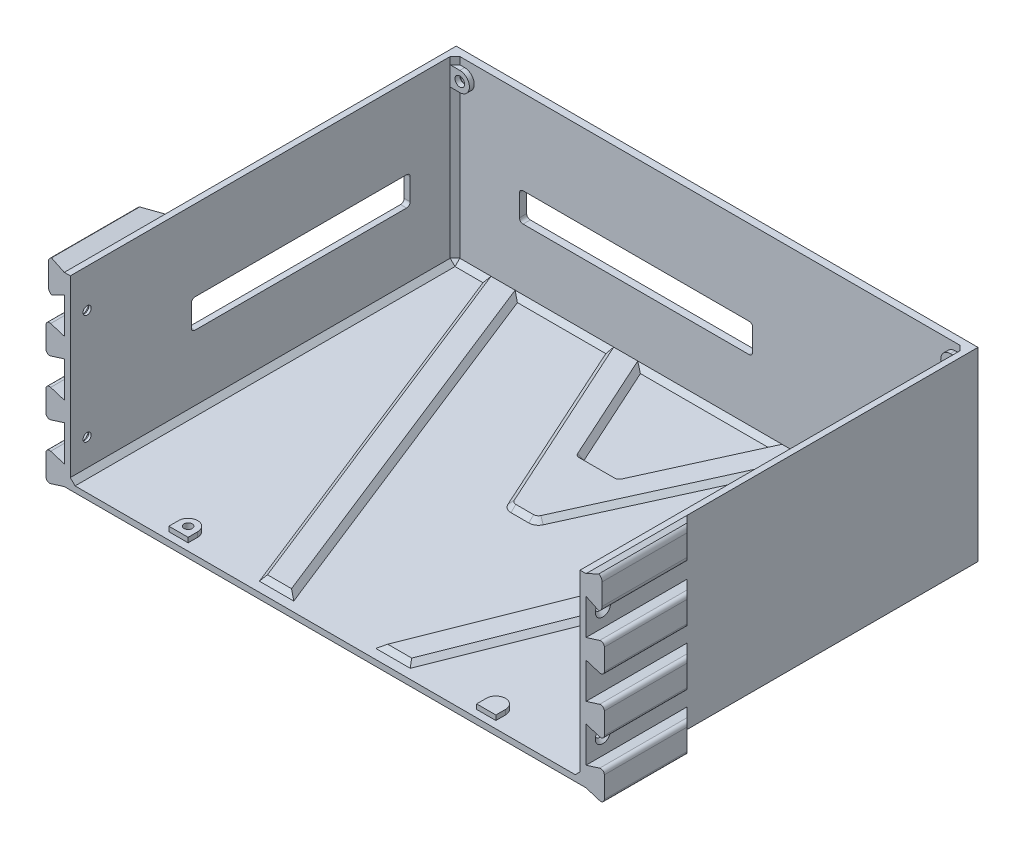
SolidWorks part; units mm, degrees
ref_plane "Płaszczyzna przednia" through (0, 0, 0) normal (0, 0, 1) x (1, 0, 0)
ref_plane "Płaszczyzna górna" through (0, 0, 0) normal (0, 1, 0) x (1, 0, 0)
ref_plane "Płaszczyzna prawa" through (0, 0, 0) normal (1, 0, 0) x (0, 0, -1)
sketch "Szkic1" plane through (0, 0, 0) normal (0, 0, 1) x (1, 0, 0)
  line L1 (0, 0) -> (217, 0)
  line L2 (0, 0) -> (0, 77.16)
  line L3 (0, 77.16) -> (217, 77.16)
  line L4 (217, 0) -> (217, 77.16)
  dimension "D1" = 77.16
  dimension "D2" = 217
extrude "Dodanie-wyciągnięcie1" add sketch "Szkic1" along normal blind 3
sketch "Szkic2" plane through (0, 0, 3) normal (0, 0, 1) x (1, 0, 0)
  line L0 (0, 77.16) -> (0, 0)
  line L1 (0, 0) -> (217, 0)
  line L2 (217, 0) -> (217, 77.16)
  line L3 (217, 77.16) -> (214.5, 77.16)
  line L4 (217, 77.16) -> (0, 77.16) construction
  line L5 (214.5, 77.16) -> (214.5, 2.5)
  line L6 (214.5, 2.5) -> (2.5, 2.5)
  line L7 (2.5, 2.5) -> (2.5, 77.16)
  line L8 (2.5, 77.16) -> (0, 77.16)
  dimension "D1" = 2.5
  dimension "D2" = 2.5
  dimension "D3" = 2.5
extrude "Dodanie-wyciągnięcie2" add sketch "Szkic2" along normal blind 160
sketch "Szkic3" plane through (0, 2.5, 0) normal (0, 1, 0) x (1, 0, 0)
  line L0 (17.5, -3) -> (78.5, -157)
  line L1 (214.5, -3) -> (2.5, -3) construction
  line L3 (27.5, -3) -> (88.5, -157)
  line L4 (214.5, -3) -> (2.5, -3) construction
  line L5 (101.1515, -50) -> (115.8485, -50)
  line L6 (78.5, -157) -> (88.5, -157)
  line L7 (17.5, -3) -> (27.5, -3)
  line L8 (199.5, -3) -> (138.5, -157)
  line L9 (138.5, -157) -> (128.5, -157)
  line L10 (128.5, -157) -> (138.5, -157)
  line L11 (128.5, -157) -> (189.5, -3)
  line L12 (189.5, -3) -> (199.5, -3)
  line L13 (217, 0) -> (0, 0) construction
  line L14 (68.5, -3) -> (102.9671, -78.8276)
  line L15 (114.0329, -78.8276) -> (148.5, -3)
  line L16 (138.5, -3) -> (117.6693, -48.8276)
  line L17 (99.3307, -48.8276) -> (78.5, -3)
  line L18 (104.7878, -80) -> (112.2122, -80)
  line L19 (68.5, -3) -> (78.5, -3)
  line L20 (138.5, -3) -> (148.5, -3)
  line L21 (108.5, 0) -> (108.5, -100) construction
  line L23 (214.5, -163) -> (2.5, -163) construction
  arc A0 (115.8485, -50) -> (117.6693, -48.8276) centre (115.8485, -48) ccw
  arc A1 (101.1515, -50) -> (99.3307, -48.8276) centre (101.1515, -48) cw
  arc A2 (112.2122, -80) -> (114.0329, -78.8276) centre (112.2122, -78) ccw
  arc A3 (104.7878, -80) -> (102.9671, -78.8276) centre (104.7878, -78) cw
  point P14 (108.5, 0)
  point P33 (113.5, -80)
  point P36 (103.5, -80)
  point P39 (108.5, -50)
  line M5 (214.5, -3) -> (2.5, -3)
  line M7 (2.5, -163) -> (214.5, -163)
  dimension "D16" = 2
  dimension "D1" = 20
  dimension "D2" = 15
  dimension "D3" = 40
  dimension "D4" = 10
  dimension "D5" = 15
  dimension "D6" = 10
  dimension "D7" = 10
  dimension "D8" = 10
  dimension "D9" = 10
  dimension "D10" = 10
  dimension "D11" = 10
  dimension "D12" = 5
  dimension "D13" = 60
  dimension "D14" = 80
  dimension "D15" = 30
  dimension "D17" = 6
extrude "Dodanie-wyciągnięcie3" add sketch "Szkic3" along normal blind 2 contours L3 L0 M5 M7 | L11 L8 M7 M5 | L20 L15 A2 L18 A3 L14 L19 L17 A1 L5 A0 L16 region at (53, 2.5, 80) region at (164, 2.5, 80)
chamfer "Sfazowanie2" distance 2 angle 45 25 edges at (169, 2.5, 80) (214.5, 39.83, 3) (214.5, 2.5, 83) (207, 2.5, 3) (58, 2.5, 80) (159, 2.5, 80) (169, 2.5, 3) (48, 2.5, 3) (48, 2.5, 80) (10, 2.5, 3) (2.5, 2.5, 83) (2.5, 39.83, 3) (108.5, 2.5, 3) (85.7335, 2.5, 40.9138) (103.7051, 2.5, 79.6815) (108.5, 2.5, 80) (113.2949, 2.5, 79.6815) (131.2665, 2.5, 40.9138) (128.0846, 2.5, 25.9138) (116.9313, 2.5, 49.6815) (108.5, 2.5, 50) (100.0687, 2.5, 49.6815) (88.9154, 2.5, 25.9138) (133.5, 2.5, 157) (83.5, 2.5, 157)
sketch "Szkic10" plane through (0, 0, 163) normal (0, 0, 1) x (1, 0, 0)
  line L0 (224.6, 87) -> (224.6, 0) construction
  line L1 (217, 0) -> (217, 77.16) construction
  line L2 (217, 0) -> (217, 8.16)
  line L3 (217, 0) -> (222.6526, -1.7665)
  line L4 (217, 8.16) -> (222.6526, 9.9265)
  line L5 (224.6, 8.4948) -> (224.6, -0.3348)
  line L6 (108.5, 77.16) -> (108.5, 114.4452) construction
  line L7 (212.5, 77.16) -> (4.5, 77.16) construction
  line L8 (217, 23) -> (217, 31.16)
  line L9 (217, 23) -> (222.6526, 21.2335)
  line L10 (217, 31.16) -> (222.6526, 32.9265)
  line L11 (224.6, 31.4948) -> (224.6, 22.6652)
  line L12 (217, 46) -> (217, 54.16)
  line L13 (217, 46) -> (222.6526, 44.2335)
  line L14 (217, 54.16) -> (222.6526, 55.9265)
  line L15 (224.6, 54.4948) -> (224.6, 45.6652)
  line L16 (-7.6, 54.4948) -> (-7.6, 45.6652)
  line L17 (0, 54.16) -> (-5.6526, 55.9265)
  line L18 (0, 46) -> (-5.6526, 44.2335)
  line L19 (0, 46) -> (0, 54.16)
  line L20 (-7.6, 31.4948) -> (-7.6, 22.6652)
  line L21 (0, 31.16) -> (-5.6526, 32.9265)
  line L22 (0, 23) -> (-5.6526, 21.2335)
  line L23 (0, 23) -> (0, 31.16)
  line L24 (-7.6, 8.4948) -> (-7.6, -0.3348)
  line L25 (0, 8.16) -> (-5.6526, 9.9265)
  line L26 (0, 0) -> (-5.6526, -1.7665)
  line L27 (0, 0) -> (0, 8.16)
  line L28 (217, 69) -> (217, 77.16)
  line L29 (217, 69) -> (222.3314, 66.4215)
  line L30 (217, 77.16) -> (222.3314, 79.7385)
  line L31 (223.6594, 77.4948) -> (223.6594, 68.6652)
  line L32 (-6.6594, 77.4948) -> (-6.6594, 68.6652)
  line L33 (0, 77.16) -> (-5.3314, 79.7385)
  line L34 (0, 69) -> (-5.3314, 66.4215)
  line L35 (0, 69) -> (0, 77.16)
  arc A0 (222.6526, -1.7665) -> (224.6, -0.3348) centre (223.1, -0.3348) ccw
  arc A1 (222.6526, 9.9265) -> (224.6, 8.4948) centre (223.1, 8.4948) cw
  arc A2 (222.6526, 21.2335) -> (224.6, 22.6652) centre (223.1, 22.6652) ccw
  arc A3 (222.6526, 32.9265) -> (224.6, 31.4948) centre (223.1, 31.4948) cw
  arc A4 (222.6526, 44.2335) -> (224.6, 45.6652) centre (223.1, 45.6652) ccw
  arc A5 (222.6526, 55.9265) -> (224.6, 54.4948) centre (223.1, 54.4948) cw
  arc A6 (-5.6526, 55.9265) -> (-7.6, 54.4948) centre (-6.1, 54.4948) ccw
  arc A7 (-5.6526, 44.2335) -> (-7.6, 45.6652) centre (-6.1, 45.6652) cw
  arc A8 (-5.6526, 32.9265) -> (-7.6, 31.4948) centre (-6.1, 31.4948) ccw
  arc A9 (-5.6526, 21.2335) -> (-7.6, 22.6652) centre (-6.1, 22.6652) cw
  arc A10 (-5.6526, 9.9265) -> (-7.6, 8.4948) centre (-6.1, 8.4948) ccw
  arc A11 (-5.6526, -1.7665) -> (-7.6, -0.3348) centre (-6.1, -0.3348) cw
  arc A12 (222.3314, 66.4215) -> (223.6594, 68.6652) centre (221.1, 68.6652) ccw
  arc A13 (222.3314, 79.7385) -> (223.6594, 77.4948) centre (221.1, 77.4948) cw
  arc A14 (-5.3314, 79.7385) -> (-6.6594, 77.4948) centre (-4.1, 77.4948) ccw
  arc A15 (-5.3314, 66.4215) -> (-6.6594, 68.6652) centre (-4.1, 68.6652) cw
  point P11 (224.6, -2.3751)
  point P14 (224.6, 10.5351)
  point P60 (-7.6, 10.5351)
  point P61 (-7.6, -2.3751)
  dimension "D5" = 1.5
  dimension "D1" = 7.6
  dimension "D2" = 8.16
  dimension "D3" = 23
  dimension "D4" = 34.71
  dimension "D6" = 3
extrude "Dodanie-wyciągnięcie6" add sketch "Szkic10" against normal blind 32
chamfer "Sfazowanie5" distance 10 angle 45 8 edges at (217, 50.08, 131) (217, 4.08, 131) (0, 4.08, 131) (0, 27.08, 131) (0, 50.08, 131) (217, 27.08, 131) (217, 73.08, 131) (0, 73.08, 131)
ref_plane "Płaszczyzna1" through (108.5, 0, 0) normal (-1, 0, 0) x (0, 0, 1)
sketch "Sketch1" plane through (0, 0, 0) normal (-1, 0, 0) x (0, 0, 1)
  line L4 (21.6472, 42.16) -> (21.6472, 33.16)
  line L5 (23.1472, 31.66) -> (111.1472, 31.66)
  line L6 (112.6472, 33.16) -> (112.6472, 42.16)
  line L7 (111.1472, 43.66) -> (23.1472, 43.66)
  line L8 (21.6472, 42.16) -> (21.6472, 33.16)
  line L9 (23.1472, 31.66) -> (111.1472, 31.66)
  line L10 (112.6472, 33.16) -> (112.6472, 42.16)
  line L11 (111.1472, 43.66) -> (23.1472, 43.66)
  arc A4 (23.1472, 43.66) -> (21.6472, 42.16) centre (23.1472, 42.16) ccw
  arc A5 (21.6472, 33.16) -> (23.1472, 31.66) centre (23.1472, 33.16) ccw
  arc A6 (111.1472, 31.66) -> (112.6472, 33.16) centre (111.1472, 33.16) ccw
  arc A7 (112.6472, 42.16) -> (111.1472, 43.66) centre (111.1472, 42.16) ccw
  arc A8 (23.1472, 43.66) -> (21.6472, 42.16) centre (23.1472, 42.16) ccw
  arc A9 (21.6472, 33.16) -> (23.1472, 31.66) centre (23.1472, 33.16) ccw
  arc A10 (111.1472, 31.66) -> (112.6472, 33.16) centre (111.1472, 33.16) ccw
  arc A11 (112.6472, 42.16) -> (111.1472, 43.66) centre (111.1472, 42.16) ccw
  dimension "D1" = 0
extrude "Cut-Extrude1" cut sketch "Sketch1" against normal up to next contours L9 A10 L10 A11 L11 A8 L8 A9
sketch "Sketch2" plane through (0, 0, 0) normal (0, 0, -1) x (-1, 0, 0)
  line L4 (-124.7972, 29.96) -> (-30.7972, 29.96)
  line L5 (-29.2972, 31.46) -> (-29.2972, 40.46)
  line L6 (-30.7972, 41.96) -> (-124.7972, 41.96)
  line L7 (-126.2972, 40.46) -> (-126.2972, 31.46)
  line L8 (-124.7972, 29.96) -> (-30.7972, 29.96)
  line L9 (-29.2972, 31.46) -> (-29.2972, 40.46)
  line L10 (-30.7972, 41.96) -> (-124.7972, 41.96)
  line L11 (-126.2972, 40.46) -> (-126.2972, 31.46)
  arc A4 (-126.2972, 31.46) -> (-124.7972, 29.96) centre (-124.7972, 31.46) ccw
  arc A5 (-30.7972, 29.96) -> (-29.2972, 31.46) centre (-30.7972, 31.46) ccw
  arc A6 (-29.2972, 40.46) -> (-30.7972, 41.96) centre (-30.7972, 40.46) ccw
  arc A7 (-124.7972, 41.96) -> (-126.2972, 40.46) centre (-124.7972, 40.46) ccw
  arc A8 (-126.2972, 31.46) -> (-124.7972, 29.96) centre (-124.7972, 31.46) ccw
  arc A9 (-30.7972, 29.96) -> (-29.2972, 31.46) centre (-30.7972, 31.46) ccw
  arc A10 (-29.2972, 40.46) -> (-30.7972, 41.96) centre (-30.7972, 40.46) ccw
  arc A11 (-124.7972, 41.96) -> (-126.2972, 40.46) centre (-124.7972, 40.46) ccw
  dimension "D1" = 0
extrude "Cut-Extrude2" cut sketch "Sketch2" against normal up to next contours L10 A11 L11 A8 L8 A9 L9 A10
sketch "Sketch3" plane through (217, 0, 0) normal (1, 0, 0) x (0, 0, -1)
  circle A0 centre (-156, 61.2082) radius 2 construction
  circle A1 centre (-156, 15.58) radius 2 construction
  circle A2 centre (-156, 61.2082) radius 2
  circle A3 centre (-156, 15.58) radius 2
sketch "Sketch4" plane through (0, 0, 0) normal (0, -1, 0) x (1, 0, 0)
  circle A1 centre (172.5, 156) radius 2 construction
  circle A2 centre (44.5, 156) radius 2 construction
  circle A3 centre (44.5, 156) radius 2
  circle A5 centre (172.5, 156) radius 2
  dimension "D1" = 4
sketch "Sketch5" plane through (0, 0, 0) normal (-1, 0, 0) x (0, 0, 1)
  circle A0 centre (156, 61.2082) radius 2 construction
  circle A1 centre (156, 15.58) radius 2 construction
  circle A2 centre (156, 61.2082) radius 2
  circle A3 centre (156, 15.58) radius 2
sketch "Sketch6" plane through (0, 0, 0) normal (-1, 0, 0) x (0, 0, 1)
  point P0 (156, 61.2082)
  point P3 (156, 15.58)
hole_wizard "CSK for M3 Countersunk Flat Head Screw1" positions "Sketch6" profile "Sketch7" countersink size "M3" standard "DIN" end condition up to next
sketch "Sketch7" plane through (0, 61.2082, 156) normal (0, 1, 0) x (0, 0, 1)
  line L0 (0, 0) -> (0, 2.5)
  line L1 (0, 2.5) -> (1.7, 2.5)
  line L2 (1.7, 2.5) -> (1.7, 1.45)
  line L3 (1.7, 1.45) -> (3.15, 0)
  line L5 (3.15, 0) -> (0, 0)
  line L6 (-1.7, 1.45) -> (-3.15, 0) construction
  line L11 (0, -6.35) -> (0, 107.95) construction
  dimension "Thru Hole Dia." = 3.4
  dimension "Thru Hole Depth" = 2.5
  dimension "Near C'Sink Dia." = 6.3
  dimension "Near C'Sink Angle" = 90
hole_wizard "CSK for M3 Countersunk Flat Head Screw2" positions "Sketch8" profile "Sketch9" countersink size "M3" standard "DIN" end condition up to next
sketch "Sketch8" plane through (0, 0, 0) normal (0, -1, 0) x (-1, 0, 0)
  point P0 (-44.5, -156)
  point P6 (-172.5, -156)
sketch "Sketch9" plane through (44.5, 0, 156) normal (1, 0, 0) x (0, 0, -1)
  line L0 (0, 0) -> (0, 2.5)
  line L1 (0, 2.5) -> (1.7, 2.5)
  line L2 (1.7, 2.5) -> (1.7, 1.45)
  line L3 (1.7, 1.45) -> (3.15, 0)
  line L5 (3.15, 0) -> (0, 0)
  line L6 (-1.7, 1.45) -> (-3.15, 0) construction
  line L11 (0, -6.35) -> (0, 107.95) construction
  dimension "Thru Hole Dia." = 3.4
  dimension "Thru Hole Depth" = 2.5
  dimension "Near C'Sink Dia." = 6.3
  dimension "Near C'Sink Angle" = 90
sketch "Sketch10" plane through (217, 0, 0) normal (1, 0, 0) x (0, 0, -1)
  point P0 (-156, 61.2082)
  point P3 (-156, 15.58)
hole_wizard "CSK for M3 Countersunk Flat Head Screw3" positions "Sketch10" profile "Sketch11" countersink size "M3" standard "DIN" end condition up to next
sketch "Sketch11" plane through (217, 61.2082, 156) normal (0, 1, 0) x (0, 0, -1)
  line L0 (0, 0) -> (0, 2.5)
  line L1 (0, 2.5) -> (1.7, 2.5)
  line L2 (1.7, 2.5) -> (1.7, 1.45)
  line L3 (1.7, 1.45) -> (3.15, 0)
  line L5 (3.15, 0) -> (0, 0)
  line L6 (-1.7, 1.45) -> (-3.15, 0) construction
  line L11 (0, -6.35) -> (0, 107.95) construction
  dimension "Thru Hole Dia." = 3.4
  dimension "Thru Hole Depth" = 2.5
  dimension "Near C'Sink Dia." = 6.3
  dimension "Near C'Sink Angle" = 90
sketch "Sketch12" plane through (0, 0, 0) normal (0, 0, -1) x (-1, 0, 0)
  circle A1 centre (-6.5, 70.16) radius 2 construction
  circle A2 centre (-210.5, 70.16) radius 2
  circle A3 centre (-6.5, 70.16) radius 2
  circle A4 centre (-210.5, 70.16) radius 2 construction
sketch "Sketch14" plane through (0, 0, 0) normal (0, 0, -1) x (-1, 0, 0)
  point P0 (-210.5, 70.16)
  point P3 (-6.5, 70.16)
hole_wizard "CSK for M3 Countersunk Flat Head Screw4" positions "Sketch14" profile "Sketch15" countersink size "M3" standard "DIN" end condition up to next
sketch "Sketch15" plane through (210.5, 70.16, 0) normal (1, 0, 0) x (0, 1, 0)
  line L0 (0, 0) -> (0, 3)
  line L1 (0, 3) -> (1.7, 3)
  line L2 (1.7, 3) -> (1.7, 1.45)
  line L3 (1.7, 1.45) -> (3.15, 0)
  line L5 (3.15, 0) -> (0, 0)
  line L6 (-1.7, 1.45) -> (-3.15, 0) construction
  line L11 (0, -6.35) -> (0, 107.95) construction
  dimension "Thru Hole Dia." = 3.4
  dimension "Thru Hole Depth" = 3
  dimension "Near C'Sink Dia." = 6.3
  dimension "Near C'Sink Angle" = 90
sketch "Sketch16" plane through (0, 2.5, 0) normal (0, 1, 0) x (1, 0, 0)
  line L0 (180.5, -160) -> (164.5, -160) construction
  line L1 (52.5, -160) -> (36.5, -160) construction
  line L2 (176.5, -160) -> (168.5, -160)
  line L3 (48.5, -160) -> (40.5, -160)
  line L4 (176.5, -156) -> (176.5, -160)
  line L5 (168.5, -156) -> (168.5, -160)
  line L6 (48.5, -156) -> (48.5, -160)
  line L7 (40.5, -156) -> (40.5, -160)
  arc A0 (172.5, -152) -> (168.5, -156) centre (172.5, -156) ccw construction
  arc A1 (176.5, -156) -> (172.5, -152) centre (172.5, -156) ccw construction
  arc A4 (44.5, -152) -> (40.5, -156) centre (44.5, -156) ccw construction
  arc A5 (48.5, -156) -> (44.5, -152) centre (44.5, -156) ccw construction
  arc A8 (172.5, -152) -> (168.5, -156) centre (172.5, -156) ccw
  arc A9 (176.5, -156) -> (172.5, -152) centre (172.5, -156) ccw
  arc A12 (44.5, -152) -> (40.5, -156) centre (44.5, -156) ccw
  arc A13 (48.5, -156) -> (44.5, -152) centre (44.5, -156) ccw
  circle A16 centre (44.5, -156) radius 1.7 construction
  circle A18 centre (44.5, -156) radius 1.7
extrude "Boss-Extrude1" add sketch "Sketch16" along normal blind 2
sketch "Sketch18" plane through (214.5, 0, 0) normal (-1, 0, 0) x (0, 0, 1)
  line L0 (160, 69.2082) -> (160, 53.2082) construction
  line L1 (160, 23.58) -> (160, 7.58) construction
  line L2 (160, 65.2082) -> (160, 57.2082)
  line L3 (160, 19.5478) -> (160, 11.58)
  line L4 (156, 11.58) -> (160, 11.58)
  line L5 (156, 19.58) -> (160, 19.5478)
  line L6 (154.65, 19.5478) -> (163.15, 19.5478) construction
  line L7 (156, 57.2082) -> (160, 57.2082)
  line L8 (156, 65.2082) -> (160, 65.2082)
  circle A0 centre (156, 61.2082) radius 1.7 construction
  circle A1 centre (156, 15.58) radius 1.7 construction
  circle A2 centre (156, 61.2082) radius 1.7
  circle A3 centre (156, 15.58) radius 1.7
  arc A5 (152, 61.2082) -> (156, 57.2082) centre (156, 61.2082) ccw construction
  arc A6 (156, 65.2082) -> (152, 61.2082) centre (156, 61.2082) ccw construction
  arc A8 (152, 15.58) -> (156, 11.58) centre (156, 15.58) ccw construction
  arc A9 (156, 19.58) -> (152, 15.58) centre (156, 15.58) ccw construction
  arc A13 (152, 61.2082) -> (156, 57.2082) centre (156, 61.2082) ccw
  arc A14 (156, 65.2082) -> (152, 61.2082) centre (156, 61.2082) ccw
  arc A16 (152, 15.58) -> (156, 11.58) centre (156, 15.58) ccw
  arc A17 (156, 19.58) -> (152, 15.58) centre (156, 15.58) ccw
extrude "Boss-Extrude3" add sketch "Sketch18" along normal blind 2
sketch "Sketch19" plane through (0, 0, 3) normal (0, 0, 1) x (1, 0, 0)
  line L0 (214.5, 66.16) -> (210.5, 66.16) construction
  line L1 (202.5, 74.16) -> (214.5, 74.16) construction
  line L2 (214.5, 74.16) -> (214.5, 66.16) construction
  line L3 (2.5, 74.16) -> (14.5, 74.16) construction
  line L4 (6.5, 66.16) -> (2.5, 66.16) construction
  line L5 (2.5, 66.16) -> (2.5, 74.16) construction
  line L6 (214.5, 66.16) -> (210.5, 66.16)
  line L7 (210.5, 74.16) -> (214.5, 74.16)
  line L8 (214.5, 74.16) -> (214.5, 66.16)
  line L9 (2.5, 74.16) -> (6.5, 74.16)
  line L10 (6.5, 66.16) -> (2.5, 66.16)
  line L11 (2.5, 66.16) -> (2.5, 74.16)
  circle A0 centre (6.5, 70.16) radius 2 construction
  circle A1 centre (210.5, 70.16) radius 1.7 construction
  circle A2 centre (6.5, 70.16) radius 2
  circle A3 centre (210.5, 70.16) radius 1.7
  arc A4 (206.5, 70.16) -> (210.5, 66.16) centre (210.5, 70.16) ccw construction
  arc A7 (6.5, 66.16) -> (10.5, 70.16) centre (6.5, 70.16) ccw construction
  arc A8 (210.5, 74.16) -> (210.5, 66.16) centre (210.5, 70.16) ccw
  arc A11 (6.5, 66.16) -> (6.5, 74.16) centre (6.5, 70.16) ccw
extrude "Boss-Extrude4" add sketch "Sketch19" along normal blind 2
